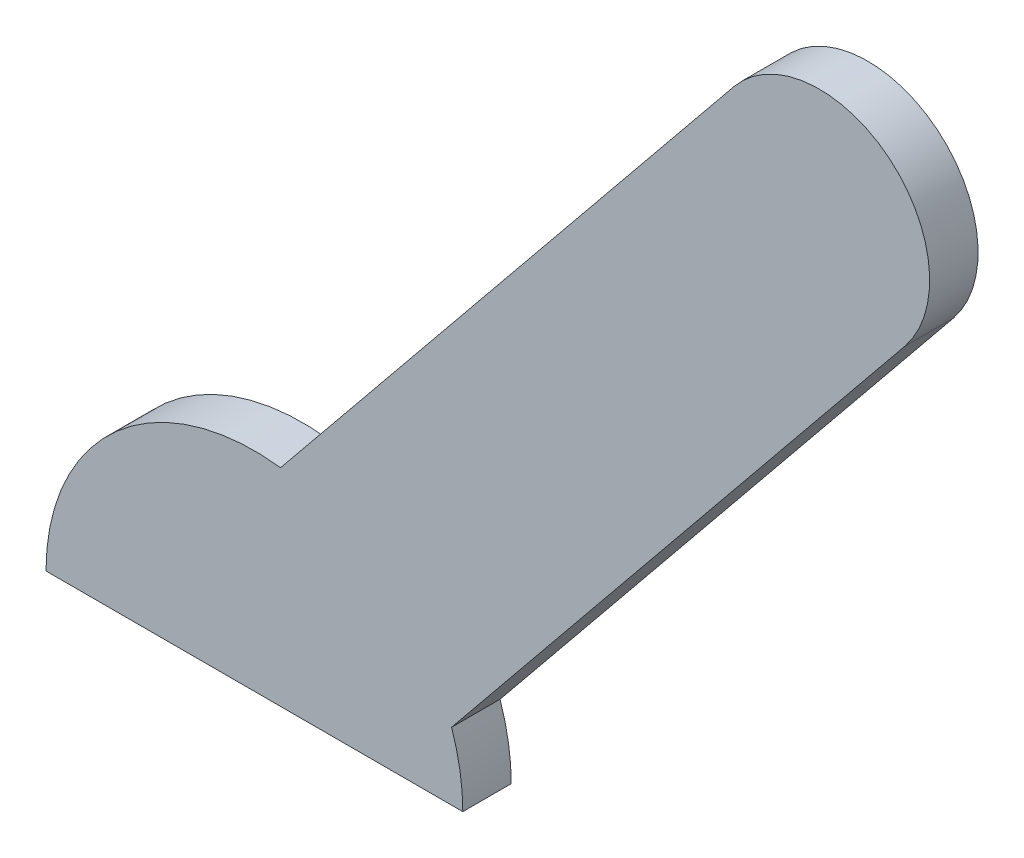
SolidWorks part; units mm, degrees
other "Markup2"
sketch "Sketch3"
ref_plane "Front Plane" through (0, 0, 0) normal (0, 0, 1) x (1, 0, 0)
ref_plane "Top Plane" through (0, 0, 0) normal (0, 1, 0) x (1, 0, 0)
ref_plane "Right Plane" through (0, 0, 0) normal (1, 0, 0) x (0, 0, -1)
sketch "Sketch1" plane through (0, 0, 0) normal (0, 0, 1) x (1, 0, 0)
  line L0 (0, 0) -> (29.6196, 36.3729) construction
  line L3 (1.3716, 10.8397) -> (25.1368, 40.0234)
  line L8 (10.3372, 3.5388) -> (34.1024, 32.7225)
  line L9 (-10.9262, 0) -> (10.9262, 0)
  line L10 (0, 0) -> (36.5473, 0) construction
  line L11 (0, 0) -> (0, 29.1314) construction
  line L12 (29.6196, 36.3729) -> (40.937, 50.2707) construction
  line L13 (29.6196, 36.3729) -> (14.8098, 48.294) construction
  arc A3 (34.1024, 32.7225) -> (25.1368, 40.0234) centre (29.6196, 36.3729) ccw
  arc A4 (-10.9262, 0) -> (10.9262, 0) centre (0, 0) cw
  text T0 "N1"
  text T1 "N2"
  text T2 "A1"
  text T3 "A2"
  point P3 (14.8098, 18.1865)
  point P17 (0, 0)
extrude "Boss-Extrude2" add sketch "Sketch1" along normal blind 2.54 contours L3 A4 L8 A3 | L9 L0 A4 | L0 L9 A4 region at (0, 4.6372, 0) region at (19.5355, 23.9896, 0)
equation "\"alpha1\"=50.843"
